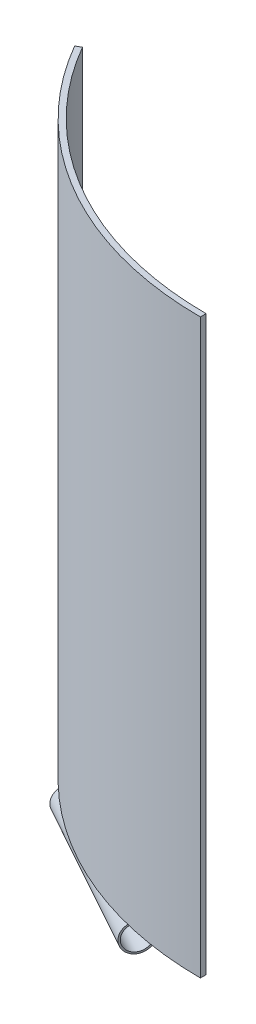
SolidWorks part; units mm, degrees
ref_plane "Front Plane" through (0, 0, 0) normal (0, 0, 1) x (1, 0, 0)
ref_plane "Top Plane" through (0, 0, 0) normal (0, 1, 0) x (1, 0, 0)
ref_plane "Right Plane" through (0, 0, 0) normal (1, 0, 0) x (0, 0, -1)
sketch "Sketch1" plane through (0, 0, 0) normal (0, 1, 0) x (1, 0, 0)
  circle A0 centre (0, 0) radius 76.2 construction
  arc A1 (0, -76.2) -> (-65.9911, -38.1) centre (0, 0) cw
extrude "Extrude-Thin1" add sketch "Sketch1" along normal blind 127 thin contours A1 thin type one direction wall 1.27
sketch "Sketch8" plane through (0, 0, 0) normal (0, 1, 0) x (1, 0, 0)
  arc A0 (0, -74.93) -> (-18.0608, -72.7208) centre (0, 0) cw construction
  arc A1 (-18.0608, -72.7208) -> (-52.0015, -53.9476) centre (0, 0) cw
extrude "Extrude-Thin2" add sketch "Sketch8" along normal blind 25.4 separate body thin contours A1 thin type one direction wall 3.81
fillet "Fillet1" radius 19.05 2 edges at (-50.6794, 25.4, 52.5761) (-17.6016, 25.4, 70.8719)
sketch "Sketch9" plane through (0, 0, 0) normal (0, -1, 0) x (1, 0, 0)
  line L1 (-49.3574, 51.2045) -> (-17.1425, 69.0231)
  line L6 (-36.2669, 65.5684) -> (-17.8863, 75.735) construction
  line L7 (-49.3574, 51.2045) -> (-17.1425, 69.0231)
  line L8 (-49.3574, 51.2045) -> (-52.3963, 56.6987)
  line L9 (-17.1425, 69.0231) -> (-20.1814, 74.5173)
  line L10 (-52.3963, 56.6987) -> (-20.1814, 74.5173)
  arc A1 (-18.0608, 72.7208) -> (-52.0015, 53.9476) centre (0, 0) ccw construction
ref_plane "Plane2" through (16.1075, 0, 8.9093) normal (0.8751, 0, 0.484) x (0.484, 0, -0.8751)
sketch "Sketch11" plane through (16.1075, 0, 8.9093) normal (0.8751, 0, 0.484) x (0.484, 0, -0.8751)
  line L0 (-68.6966, 0) -> (-71.8716, 0) construction
  line L1 (-71.8716, 0) -> (-71.8716, -3.175)
  circle A0 centre (-71.8716, -3.175) radius 3.175
extrude "Boss-Extrude3" add sketch "Sketch11" against normal blind 37.846 and the other way blind 0.762 separate body contours A0
sketch "Sketch13" plane through (-17.0101, 0, -9.4086) normal (-0.8751, 0, -0.484) x (-0.484, 0, 0.8751)
  line L0 (71.8716, 0) -> (71.8716, -3.175) construction
  line L1 (72.3768, 0) -> (68.6966, 0) construction
  circle A0 centre (71.8716, -3.175) radius 3.175 construction
  circle A1 centre (71.8716, -3.175) radius 2.794
extrude "Cut-Extrude1" cut sketch "Sketch13" against normal blind 43.18 contours A1
